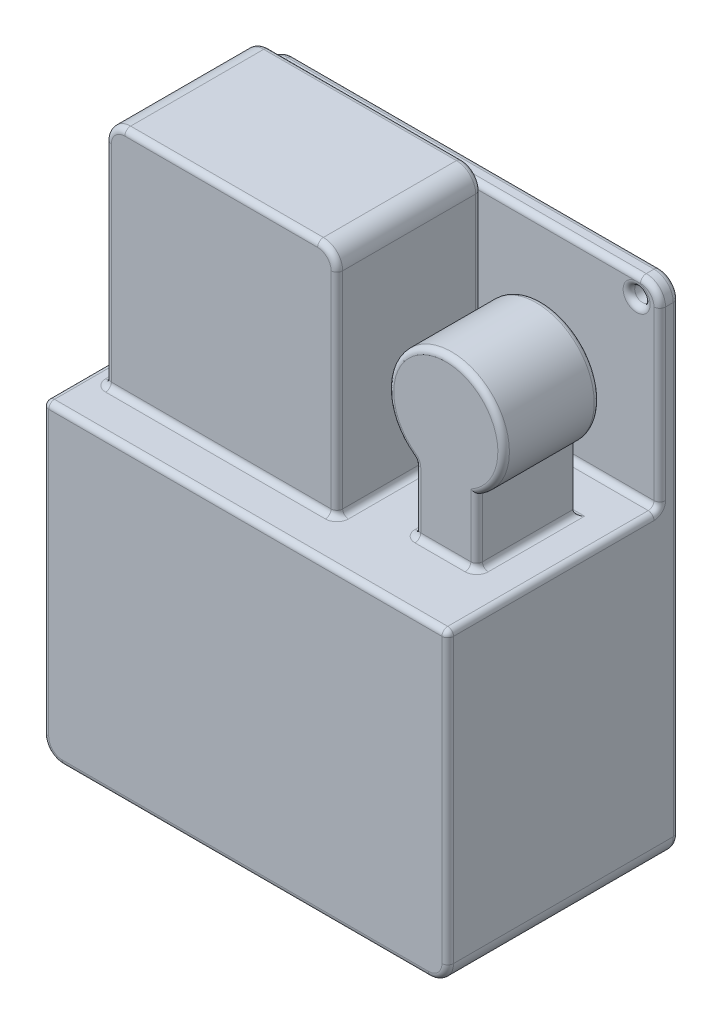
SolidWorks part; units mm, degrees
ref_plane "前视基准面" through (0, 0, 0) normal (0, 0, 1) x (1, 0, 0)
ref_plane "上视基准面" through (0, 0, 0) normal (0, 1, 0) x (1, 0, 0)
ref_plane "右视基准面" through (0, 0, 0) normal (1, 0, 0) x (0, 0, -1)
sketch "草图1" plane through (0, 0, 0) normal (0, 0, 1) x (1, 0, 0)
  line L1 (-105, 80) -> (105, 80)
  line L2 (-105, 80) -> (-105, -80)
  line L3 (-105, -80) -> (105, -80)
  line L4 (105, 80) -> (105, -80)
  line L5 (-105, 80) -> (105, -80) construction
  line L6 (-105, -80) -> (105, 80) construction
  point P0 (0, 0)
  dimension "D1" = 160
  dimension "D2" = 210
extrude "凸台-拉伸1" add sketch "草图1" along normal mid plane 120
sketch "草图2" plane through (0, 80, 0) normal (0, 1, 0) x (1, 0, 0)
  line L0 (0, 0) -> (-105, 0) construction
  line L1 (-105, -60) -> (-105, 60) construction
  line L3 (-95, 37.5) -> (25, 37.5)
  line L4 (-95, 37.5) -> (-95, -37.5)
  line L5 (-95, -37.5) -> (25, -37.5)
  line L6 (25, 37.5) -> (25, -37.5)
  line L7 (-95, 37.5) -> (25, -37.5) construction
  line L8 (-95, -37.5) -> (25, 37.5) construction
  point P5 (-35, 0)
  dimension "D1" = 70
  dimension "D2" = 120
  dimension "D3" = 75
extrude "凸台-拉伸2" add sketch "草图2" along normal blind 120
sketch "草图3" plane through (0, 0, 0) normal (0, 0, 1) x (1, 0, 0)
  line L0 (105, 80) -> (-105, 80) construction
  line L1 (105, -80) -> (105, 80) construction
  line L2 (53, 114) -> (53, 80)
  line L3 (53, 80) -> (85, 80)
  line L4 (85, 114) -> (85, 80)
  line L5 (69, 139.3772) -> (69, 80) construction
  arc A0 (85, 114) -> (53, 114) centre (69, 139.3772) ccw
  point P1 (54.1989, 80)
  point P5 (90.1038, 114.0253)
  point P8 (89.5295, 80)
  dimension "D2" = 30
  dimension "D1" = 32
  dimension "D3" = 34
  dimension "D4" = 20
extrude "凸台-拉伸3" add sketch "草图3" along normal mid plane 50
sketch "草图4" plane through (0, 80, 0) normal (0, 1, 0) x (1, 0, 0)
  line L0 (105, -60) -> (105, 60) construction
  line L1 (-105, 60) -> (105, 60)
  line L2 (-105, 60) -> (-105, 50)
  line L3 (-105, 50) -> (105, 50)
  line L4 (105, 60) -> (105, 50)
  dimension "D1" = 10
extrude "凸台-拉伸4" add sketch "草图4" along normal blind 100
sketch "草图5" plane through (0, 0, -60) normal (0, 0, -1) x (-1, 0, 0)
  line L0 (0, 180) -> (0, 170) construction
  line L1 (-105, 180) -> (105, 180) construction
  line L2 (-93, 170) -> (93, 170) construction
  circle A0 centre (-93, 170) radius 4
  circle A1 centre (93, 170) radius 4
  point P8 (0, 170)
  dimension "D3" = 8
  dimension "D4" = 8
  dimension "D1" = 10
  dimension "D2" = 186
extrude "切除-拉伸1" cut sketch "草图5" against normal blind 12
fillet "圆角1" radius 10 6 edges at (105, -80, 0) (-105, -80, 0) (-95, 200, 0) (25, 200, 0) (-105, 180, -55) (105, 180, -55)
fillet "圆角4" radius 3 50 edges at (0, -80, -60) (102.0711, -77.0711, -60) (105, 50, -60) (25, 135, -37.5) (-97, 170, -60) (-97, 170, -50) (89, 170, -60) (89, 170, -50) (0, 80, -50) (0, 180, -50) (0, 180, -60) (105, 125, -50) (-105, 125, -50) (69, 169.3772, -25) (53, 97, -25) (69, 80, -25) (69, 169.3772, 25) (53, 97, 25) (69, 80, 25) (85, 97, 25) (85, 80, 0) (53, 80, 0) (53, 114, 0) (25, 80, 0) (-35, 80, -37.5) (-95, 80, 0) (-35, 80, 37.5) (-35, 200, -37.5) (-35, 200, 37.5) (25, 135, 37.5) (-95, 135, 37.5) (-95, 135, -37.5) (-105, 50, -60) (105, 5, 60) (0, 80, 60) (-105, 5, 60) (0, -80, 60) (-105, 80, 5) (105, 80, 5) (102.0711, 177.0711, -60) (-102.0711, 177.0711, -60) (-102.0711, -77.0711, -60) (-102.0711, -77.0711, 60) (102.0711, -77.0711, 60) (22.0711, 197.0711, 37.5) (-92.0711, 197.0711, 37.5) (22.0711, 197.0711, -37.5) (-92.0711, 197.0711, -37.5) (102.0711, 177.0711, -50) (-102.0711, 177.0711, -50)
